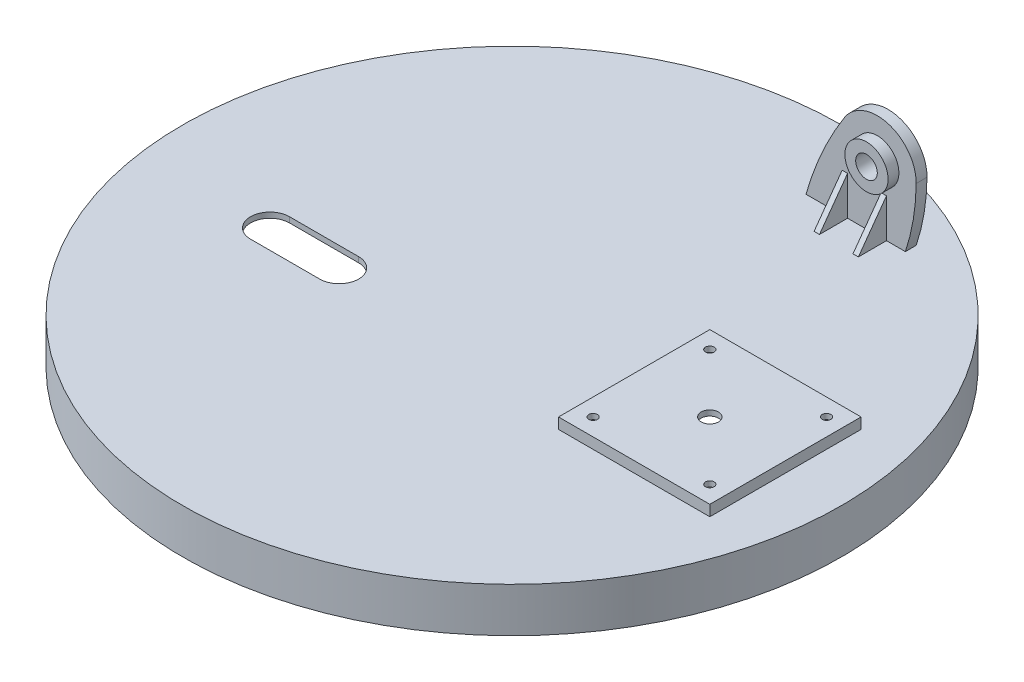
SolidWorks part; units mm, degrees
ref_plane "前视基准面" through (0, 0, 0) normal (0, 0, 1) x (1, 0, 0)
ref_plane "上视基准面" through (0, 0, 0) normal (0, 1, 0) x (1, 0, 0)
ref_plane "右视基准面" through (0, 0, 0) normal (1, 0, 0) x (0, 0, -1)
sketch "草图1" plane through (0, 0, 0) normal (0, 1, 0) x (1, 0, 0)
  circle A0 centre (0, 0) radius 305
  dimension "D1" = 610
extrude "凸台-拉伸1" add sketch "草图1" along normal blind 41.2
sketch "草图2" plane through (0, 41.2, 0) normal (0, 1, 0) x (1, 0, 0)
  line L1 (113, -70) -> (253, -70)
  line L2 (113, -70) -> (113, 70)
  line L3 (113, 70) -> (253, 70)
  line L4 (253, -70) -> (253, 70)
  line L5 (113, -70) -> (253, 70) construction
  line L6 (113, 70) -> (253, -70) construction
  point P0 (183, 0)
  dimension "D1" = 140
  dimension "D2" = 113
extrude "凸台-拉伸2" add sketch "草图2" along normal blind 10
shell "抽壳1" thickness 5 removed face at (0, 0, 305)
sketch "草图3" plane through (0, 41.2, 0) normal (0, 1, 0) x (1, 0, 0)
  line L0 (-182, -42) -> (-118, -42) construction
  line L1 (-182, -24) -> (-118, -24)
  line L2 (-182, -60) -> (-118, -60)
  arc A0 (-182, -24) -> (-182, -60) centre (-182, -42) ccw
  arc A1 (-118, -60) -> (-118, -24) centre (-118, -42) ccw
  point P2 (-150, -42)
  dimension "D1" = 100
  dimension "D4" = 100
  dimension "D2" = 36
  dimension "D3" = 42
extrude "切除-拉伸1" cut sketch "草图3" against normal blind 10
sketch "草图4" plane through (0, 41.2, 0) normal (0, 1, 0) x (1, 0, 0)
  line L1 (39, 243) -> (159, 243)
  line L2 (39, 243) -> (39, 233)
  line L3 (39, 233) -> (159, 233)
  line L4 (159, 243) -> (159, 233)
  dimension "D1" = 39
  dimension "D2" = 243
  dimension "D3" = 10
  dimension "D4" = 120
extrude "凸台-拉伸3" add sketch "草图4" along normal blind 150
sketch "草图5" plane through (0, 0, -233) normal (0, 0, 1) x (1, 0, 0)
  line L0 (39, 191.2) -> (39, 41.2) construction
  line L1 (39, 41.2) -> (159, 41.2) construction
  line L3 (131, 41.2) -> (159.0682, 41.2)
  line L4 (113, 41.2) -> (253, 41.2) construction
  line L5 (159.0682, 41.2) -> (159, 191.2)
  line L6 (159, 191.2) -> (39, 191.2)
  line L7 (39, 191.2) -> (39, 41.2)
  arc A0 (39, 41.2) -> (74.6468, 120.5567) centre (327.5902, -40.7493) cw
  arc A1 (74.6468, 120.5567) -> (140.998, 100.8218) centre (105, 101.2) cw
  arc A2 (140.998, 100.8218) -> (131, 41.2) centre (-53.9912, 102.8705) cw
  dimension "D2" = 300
  dimension "D3" = 36
  dimension "D4" = 195
  dimension "D1" = 105
  dimension "D5" = 92
  dimension "D6" = 60
extrude "切除-拉伸3" cut sketch "草图5" against normal through all
sketch "草图6" plane through (0, 0, -233) normal (0, 0, 1) x (1, 0, 0)
  circle A0 centre (105, 101.2) radius 10
  dimension "D1" = 20
extrude "切除-拉伸4" cut sketch "草图6" against normal blind 150
sketch "草图7" plane through (0, 0, -233) normal (0, 0, 1) x (1, 0, 0)
  circle A0 centre (105, 101.2) radius 20
  circle A1 centre (105, 101.2) radius 10 construction
  circle A2 centre (105, 101.2) radius 10
  dimension "D1" = 40
extrude "凸台-拉伸4" add sketch "草图7" along normal blind 10
sketch "草图8" plane through (0, 0, -233) normal (0, 0, 1) x (1, 0, 0)
  line L0 (39, 41.2) -> (131, 41.2) construction
  line L1 (72.5, 41.2) -> (77.5, 41.2)
  line L2 (72.5, 41.2) -> (72.5, 77.2)
  line L3 (72.5, 77.2) -> (77.5, 77.2)
  line L4 (77.5, 41.2) -> (77.5, 77.2)
  line L6 (108.5, 41.2) -> (113.5, 41.2)
  line L7 (108.5, 41.2) -> (108.5, 77.2)
  line L8 (108.5, 77.2) -> (113.5, 77.2)
  line L9 (113.5, 41.2) -> (113.5, 77.2)
  point P10 (75, 41.2)
  point P14 (111, 41.2)
  dimension "D1" = 75
  dimension "D2" = 36
  dimension "D3" = 5
  dimension "D4" = 36
extrude "凸台-拉伸5" add sketch "草图8" along normal blind 26
sketch "草图9" plane through (113.5, 0, 0) normal (1, 0, 0) x (0, 0, -1)
  line L0 (207, 41.2) -> (233, 77.2)
  line L1 (233, 100.8218) -> (233, 41.2) construction
  line L2 (233, 41.2) -> (233, 77.2) construction
  line L3 (207, 41.2) -> (207, 77.2) construction
  line L4 (207, 41.2) -> (233, 41.2) construction
  line L5 (207, 77.2) -> (233, 77.2) construction
  line L6 (233, 77.2) -> (207, 77.2)
  line L7 (207, 77.2) -> (207, 41.2)
extrude "切除-拉伸5" cut sketch "草图9" against normal through all
sketch "草图10" plane through (0, 0, 0) normal (0, 0, 1) x (1, 0, 0)
  line L0 (0, 0) -> (0, 41.2) construction
  line L1 (-305, 0) -> (305, 0) construction
  line L2 (305, 41.2) -> (-305, 41.2) construction
  line L3 (-56, 36.2) -> (-56, 31.2)
  line L4 (-56, 31.2) -> (-75, 31.2)
  line L5 (-75, 31.2) -> (-75, 36.2)
  line L6 (-75, 36.2) -> (-56, 36.2)
  line L7 (-80, 36.2) -> (-80, -10.3)
  line L8 (-80, -10.3) -> (-85, -10.3)
  line L9 (-85, -10.3) -> (-85, 36.2)
  line L10 (-85, 36.2) -> (-80, 36.2)
  dimension "D1" = 5
  dimension "D2" = 150
  dimension "D3" = 170
  dimension "D4" = 5
  dimension "D5" = 19
  dimension "D6" = 5
  dimension "D7" = 51.5
revolve "旋转1" add sketch "草图10" angle 360 about L0
sketch "草图11" plane through (0, 51.2, 0) normal (0, 1, 0) x (1, 0, 0)
  line L0 (113, 70) -> (253, -70) construction
  line L1 (129, -54) -> (237, -54) construction
  line L2 (129, -54) -> (129, 54) construction
  line L3 (129, 54) -> (237, 54) construction
  line L4 (237, -54) -> (237, 54) construction
  line L5 (129, -54) -> (237, 54) construction
  line L6 (129, 54) -> (237, -54) construction
  circle A0 centre (183, 0) radius 8
  circle A1 centre (237, 54) radius 4
  circle A2 centre (237, -54) radius 4
  circle A3 centre (129, -54) radius 4
  circle A4 centre (129, 54) radius 4
  point P0 (183, 0)
  dimension "D2" = 8
  dimension "D3" = 16
  dimension "D1" = 108
extrude "切除-拉伸6" cut sketch "草图11" against normal blind 26
equation "\"41。2\"=10"
